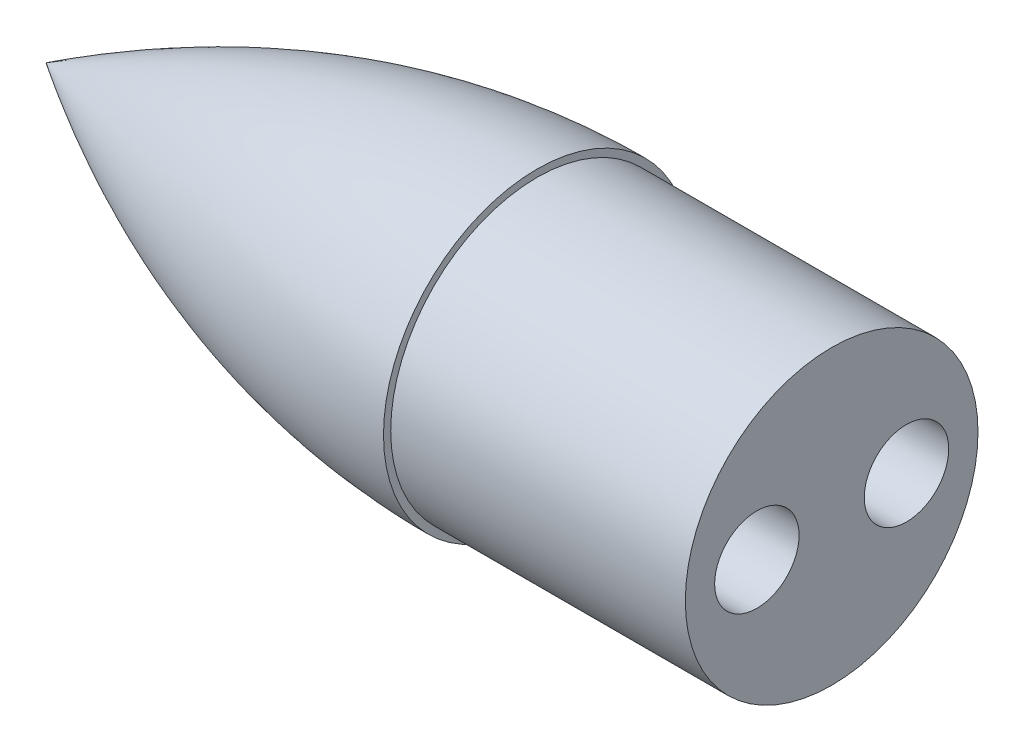
SolidWorks part; units mm, degrees
ref_plane "Front Plane" through (0, 0, 0) normal (0, 0, 1) x (1, 0, 0)
ref_plane "Top Plane" through (0, 0, 0) normal (0, 1, 0) x (1, 0, 0)
ref_plane "Right Plane" through (0, 0, 0) normal (1, 0, 0) x (0, 0, -1)
sketch "Sketch1" plane through (0, 0, 0) normal (0, 0, 1) x (1, 0, 0)
  line L0 (0, 0) -> (127, 0) construction
  line L1 (127, 0) -> (127, 39.7129)
  line L2 (0, 0) -> (127, 0)
  spline S0 degree 2 poles (-11.3074, -7.3864) (64.1963, 44.0378) (139.7, 39.3158) knots 0 0 0 1 1 1 construction
  spline S1 degree 2 poles (0, 0) (63.5, 39.7129) (127, 39.7129) knots 0.074879 0.074879 0.074879 0.915898 0.915898 0.915898
revolve "Revolve1" add sketch "Sketch1" angle 360 about L0
sketch "Sketch2" plane through (127, 0, 0) normal (1, 0, 0) x (0, 0, -1)
  circle A0 centre (0, 0) radius 37.846
  dimension "D1" = 75.692
extrude "Boss-Extrude1" add sketch "Sketch2" along normal blind 50.8
sketch "Sketch3" plane through (177.8, 0, 0) normal (1, 0, 0) x (0, 0, -1)
  line L0 (0, 0) -> (0, 29.5161) construction
  circle A0 centre (-19.3476, 0) radius 10.922
  dimension "D2" = 21.844
  dimension "D1" = 19.3476
revolve "Cut-Revolve1" cut sketch "Sketch3" angle 360 about L0
sketch "Sketch4" plane through (177.8, 0, 0) normal (1, 0, 0) x (0, 0, -1)
  circle A0 centre (-19.3476, 0) radius 10.922
  circle A1 centre (19.3476, 0) radius 10.922
  circle A2 centre (0, 0) radius 37.846
  circle M3 centre (-19.3476, 0) radius 10.922
  circle M4 centre (19.3476, 0) radius 10.922
  dimension "D1" = 75.692
  dimension "D2" = 21.844
  dimension "D3" = 21.844
extrude "Boss-Extrude2" add sketch "Sketch4" along normal blind 25.4 contours M4 | M3 | A2 region at (177.8, 0, 19.3476) region at (177.8, 0, -19.3476)
